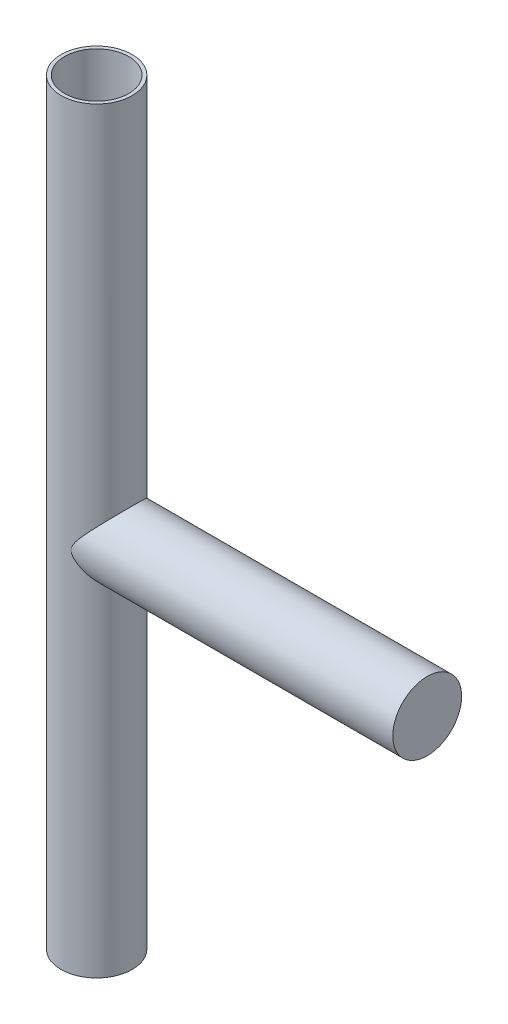
SolidWorks part; units mm, degrees
ref_plane "Front Plane" through (0, 0, 0) normal (0, 0, 1) x (1, 0, 0)
ref_plane "Top Plane" through (0, 0, 0) normal (0, 1, 0) x (1, 0, 0)
ref_plane "Right Plane" through (0, 0, 0) normal (1, 0, 0) x (0, 0, -1)
sketch "Sketch1" plane through (0, 0, 0) normal (0, 1, 0) x (1, 0, 0)
  circle A0 centre (0, 0) radius 7.75
  circle A1 centre (0, 0) radius 7
  dimension "D1" = 15.5
  dimension "D2" = 14
extrude "Boss-Extrude1" add sketch "Sketch1" along normal blind 160 and the other way blind 5
sketch "Sketch5" plane through (0, 0, 0) normal (1, 0, 0) x (0, 0, -1)
  circle A0 centre (0, 75) radius 7.5
  dimension "D1" = 15
extrude "Boss-Extrude3" add sketch "Sketch5" along normal blind 72.0622
